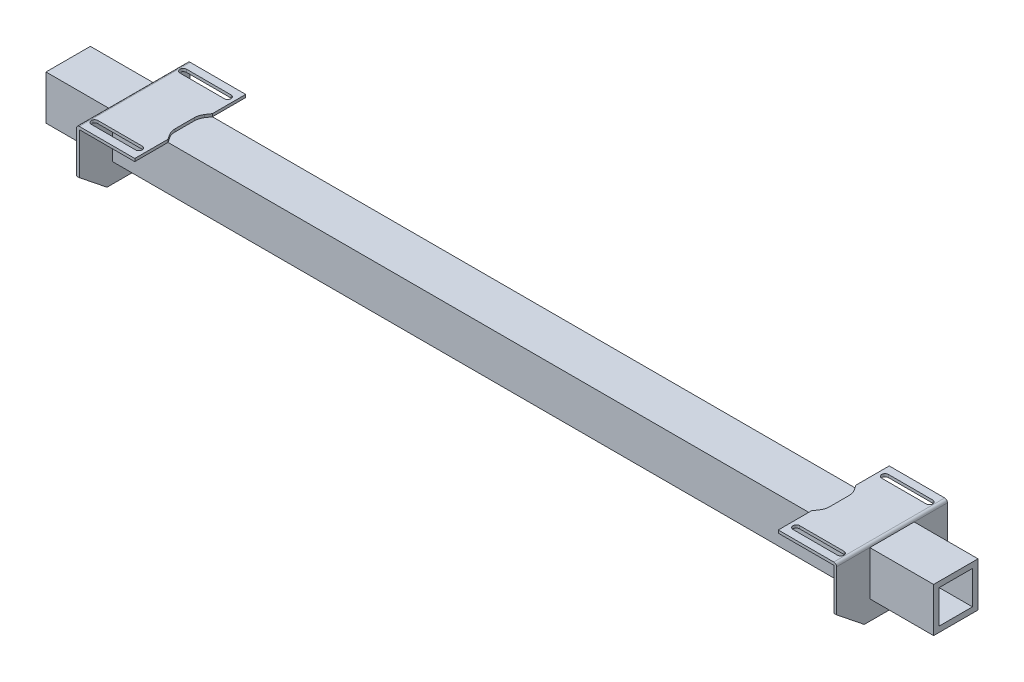
SolidWorks part; units mm, degrees
ref_plane "Front Plane" through (0, 0, 0) normal (0, 0, 1) x (1, 0, 0)
ref_plane "Top Plane" through (0, 0, 0) normal (0, 1, 0) x (1, 0, 0)
ref_plane "Right Plane" through (0, 0, 0) normal (1, 0, 0) x (0, 0, -1)
sketch "Sketch3" plane through (0, 0, 0) normal (1, 0, 0) x (0, 0, -1)
  line L1 (0, 0) -> (80, 0)
  line L2 (0, 0) -> (0, 80)
  line L3 (0, 80) -> (80, 80)
  line L4 (80, 0) -> (80, 80)
  line L5 (10, 70) -> (70, 70)
  line L6 (10, 70) -> (10, 10)
  line L7 (10, 10) -> (70, 10)
  line L8 (70, 70) -> (70, 10)
  dimension "D1" = 80
  dimension "D2" = 80
  dimension "D3" = 10
  dimension "D4" = 10
  dimension "D5" = 10
  dimension "D6" = 10
extrude "Boss-Extrude2" add sketch "Sketch3" along normal blind 1600
ref_plane "Plane1" through (1480, 0, 0) normal (1, 0, 0) x (0, 0, -1)
sketch "Sketch7" plane through (1480, 0, 0) normal (1, 0, 0) x (0, 0, -1)
  line L0 (-60, 85) -> (140, 85)
  line L1 (140, 85) -> (140, 5)
  line L2 (140, 5) -> (90, -35)
  line L3 (90, -35) -> (-10, -35)
  line L4 (-10, -35) -> (-60, 5)
  line L5 (-60, 5) -> (-60, 85)
  line L6 (80, 80) -> (0, 80) construction
  line L7 (70, 70) -> (10, 70) construction
  line L8 (70, 70) -> (10, 70)
  line L9 (70, 10) -> (70, 70) construction
  line L10 (10, 10) -> (70, 10) construction
  line L11 (10, 70) -> (10, 10) construction
  line L12 (70, 10) -> (70, 70)
  line L13 (10, 10) -> (70, 10)
  line L14 (10, 70) -> (10, 10)
  point P10 (40, 85)
  point P11 (40, 80)
  dimension "D1" = 200
  dimension "D2" = 120
  dimension "D3" = 50
  dimension "D4" = 50
  dimension "D5" = 5
  dimension "D6" = 40
extrude "Boss-Extrude3" add sketch "Sketch7" along normal blind 5
sketch "Sketch8" plane through (0, 0, -80) normal (0, 0, -1) x (-1, 0, 0)
  line L0 (-1485, 85) -> (-1480, 85) construction
  line L1 (-1485, 85) -> (-1380, 85)
  line L2 (-1485, 85) -> (-1485, 80)
  line L3 (-1485, 80) -> (-1380, 80)
  line L4 (-1380, 85) -> (-1380, 80)
  line L5 (-1485, 5) -> (-1485, 85) construction
  dimension "D1" = 5
  dimension "D2" = 105
extrude "Boss-Extrude4" add sketch "Sketch8" along normal up to surface and the other way up to surface up to face at (1482.5, 45, -140) other way up to face at (1482.5, 45, 60)
sketch "Sketch9" plane through (0, 85, 0) normal (0, 1, 0) x (1, 0, 0)
  line L0 (1380, 80) -> (1385.8013, 71.2981)
  line L1 (1380, 140) -> (1380, -60) construction
  line L2 (1390, 57.4306) -> (1390, 22.5694)
  line L3 (1385.8013, 8.7019) -> (1380, 0)
  line L4 (1380, 0) -> (0, 0) construction
  line L5 (1380, 0) -> (1380, 80)
  line L6 (1600, 80) -> (1600, 0) construction
  arc A0 (1390, 22.5694) -> (1385.8013, 8.7019) centre (1365, 22.5694) cw
  arc A1 (1385.8013, 71.2981) -> (1390, 57.4306) centre (1365, 57.4306) cw
  point P15 (1390, 15)
  point P18 (1390, 65)
  dimension "D4" = 25
  dimension "D1" = 10
  dimension "D2" = 15
  dimension "D3" = 15
extrude "Cut-Extrude1" cut sketch "Sketch9" against normal up to surface (5 mm away) up to face at (1430, 80, 30)
sketch "Sketch10" plane through (0, 85, 0) normal (0, 1, 0) x (1, 0, 0)
  line L0 (1392.5, 120) -> (1472.5, 120) construction
  line L1 (1392.5, 126) -> (1472.5, 126)
  line L2 (1392.5, 114) -> (1472.5, 114)
  line L3 (1392.5, -40) -> (1472.5, -40) construction
  line L4 (1392.5, -34) -> (1472.5, -34)
  line L5 (1392.5, -46) -> (1472.5, -46)
  line L6 (1485, 140) -> (1380, 140) construction
  arc A0 (1392.5, 126) -> (1392.5, 114) centre (1392.5, 120) ccw
  arc A1 (1472.5, 114) -> (1472.5, 126) centre (1472.5, 120) ccw
  arc A2 (1392.5, -34) -> (1392.5, -46) centre (1392.5, -40) ccw
  arc A3 (1472.5, -46) -> (1472.5, -34) centre (1472.5, -40) ccw
  point P2 (1432.5, 120)
  point P7 (1432.5, -40)
  point P16 (1432.5, 140)
  point P17 (1432.5, 126)
  dimension "D1" = 80
  dimension "D2" = 12
  dimension "D3" = 12
  dimension "D4" = 160
  dimension "D5" = 20
extrude "Cut-Extrude2" cut sketch "Sketch10" against normal up to next
fillet "Fillet1" radius 5 1 edges at (1485, 85, -40)
ref_plane "Plane2" through (800, 0, 0) normal (1, 0, 0) x (0, 0, -1)
mirror "Mirror1" about plane through (800, 0, 0) normal (1, 0, 0) of "Fillet1", "Boss-Extrude3"
mirror "Mirror2" about plane through (800, 0, 0) normal (1, 0, 0) of "Fillet1", "Cut-Extrude2", "Boss-Extrude3", "Boss-Extrude4", "Cut-Extrude1"
sketch "Sketch13" plane through (0, 0, 0) normal (0, 0, 1) x (1, 0, 0)
  line L0 (0, 40) -> (2446.8223, 40) construction
  line L1 (0, 80) -> (0, 0) construction
sketch "Sketch14" plane through (0, 80, 0) normal (0, 1, 0) x (1, 0, 0)
  line L0 (800, 80) -> (800, 0) construction
  line L1 (1480, 80) -> (120, 80) construction
  line L2 (1480, 0) -> (120, 0) construction
  line L3 (706.4267, 40) -> (893.5733, 40) construction
  point P8 (800, 40)
equation "\"D2@Sketch3\"=\"D1@Sketch3\""
equation "\"D4@Sketch3\"=\"D3@Sketch3\""
equation "\"D5@Sketch3\"=\"D3@Sketch3\""
equation "\"D6@Sketch3\"=\"D3@Sketch3\""
equation "\"D3@Sketch9\"=\"D2@Sketch9\""
